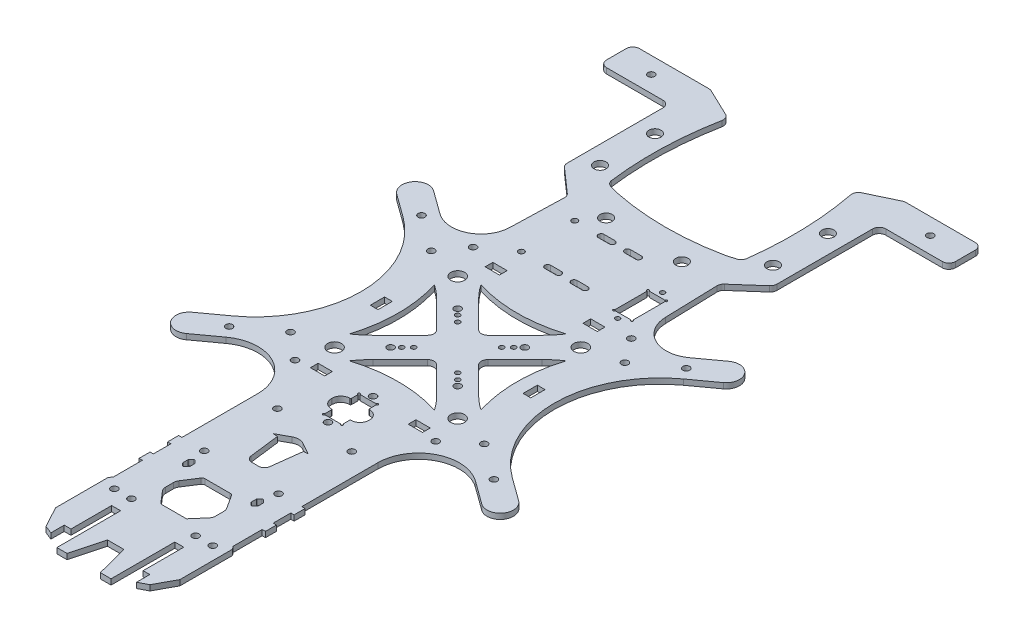
SolidWorks part; units mm, degrees
ref_plane "前视基准面" through (0, 0, 0) normal (0, 0, 1) x (1, 0, 0)
ref_plane "上视基准面" through (0, 0, 0) normal (0, 1, 0) x (1, 0, 0)
ref_plane "右视基准面" through (0, 0, 0) normal (1, 0, 0) x (0, 0, -1)
sketch "草图1" plane through (0, 0, 0) normal (0, 1, 0) x (1, 0, 0)
  line L0 (-126.4995, 0) -> (116.8967, 0) construction
  line L1 (121.619, 121.619) -> (-121.619, -121.619) construction
  line L2 (0, 104.5414) -> (0, -99.6328) construction
  line L3 (-108.3893, 108.3893) -> (124.9236, -124.9236) construction
  line L4 (0, 0) -> (86.3378, -62.728) construction
  line L5 (21.4, 65.75) -> (28.6, 65.75)
  line L6 (20.9, 50.75) -> (20.9, 65.25)
  line L19 (21.4, 50.25) -> (28.6, 50.25)
  line L20 (34.6494, 84.6384) -> (47.6818, 96.1449)
  line L21 (0, 82.79) -> (0, 88.225) construction
  line L22 (17.0991, -107.7737) -> (17.0991, -105.6162)
  line L23 (-24.5433, 97.1224) -> (-30.4982, 98.8019)
  line L24 (44.1232, 159.0629) -> (28.8407, 151.7785)
  line L25 (27.2573, -98.177) -> (28.7573, -98.177)
  line L26 (35.4016, 59.0549) -> (34.6494, 84.6384)
  line L27 (79.3904, 159.0629) -> (44.1232, 159.0629)
  line L28 (15.9026, -104.2126) -> (16.9526, -105.2626)
  line L29 (14.1455, -105.2626) -> (15.1955, -104.2126)
  line L30 (-16.9545, -108.1273) -> (-15.9045, -109.1773)
  line L31 (79.3904, 144.0629) -> (79.3904, 159.0629)
  line L32 (27.2573, -98.177) -> (27.2573, -63.5957)
  line L33 (67.2151, -56.251) -> (56.6859, -48.6011)
  line L34 (47.6818, 144.0629) -> (79.3904, 144.0629)
  line L35 (74.2685, -46.5428) -> (63.7393, -38.8929)
  line L36 (-15.1974, -109.1773) -> (-14.1474, -108.1273)
  line L37 (-14.0009, -105.6162) -> (-14.0009, -107.7737)
  line L38 (-14.1474, -105.2626) -> (-15.1974, -104.2126)
  line L39 (-47.6818, 96.1449) -> (-47.6818, 144.0629)
  line L40 (-34.6494, 84.6384) -> (-47.6818, 96.1449)
  line L41 (-35.4016, 59.0549) -> (-34.6494, 84.6384)
  line L42 (28.7573, -98.177) -> (28.7573, -103.177)
  line L59 (0, 72.0242) -> (0, 60.8242) construction
  line L64 (20.9, 58) -> (32.4846, 58) construction
  line L65 (25, 65.75) -> (25, 50.25) construction
  line L66 (29.1, 65.25) -> (29.1, 50.75)
  line L69 (-28.3, 64.3716) -> (-2.5276, 64.3716) construction
  line L72 (28.7573, -103.177) -> (27.2573, -103.177)
  line L80 (-15.9045, -104.2126) -> (-16.9545, -105.2626)
  line L81 (-17.1009, -107.7737) -> (-17.1009, -105.6162)
  line L82 (4.1009, -56.25) -> (4.1009, -53.2975)
  line L83 (-3.6009, -56.75) -> (3.6009, -56.75)
  line L84 (3.6009, -40.75) -> (-3.5991, -40.75)
  line L85 (4.1009, -41.25) -> (4.1009, -44.2025)
  line L86 (-4.1009, -56.25) -> (-4.1009, -53.2961)
  line L87 (-4.1009, -44.2011) -> (-4.1009, -41.2481)
  line L88 (-4.5484, -52.9461) -> (-4.4509, -52.9461)
  line L89 (-8.5484, -48.9461) -> (-8.5484, -48.5511)
  line L90 (8.5484, -48.9475) -> (8.5484, -48.5525)
  line L91 (4.4509, -52.9475) -> (4.5484, -52.9475)
  line L92 (4.5484, -44.5525) -> (4.4509, -44.5525)
  line L93 (-4.5484, -44.5511) -> (-4.4509, -44.5511)
  line L94 (13.9991, -105.6162) -> (13.9991, -107.7737)
  line L95 (15.1955, -109.1773) -> (14.1455, -108.1273)
  line L96 (16.9526, -108.1273) -> (15.9026, -109.1773)
  line L97 (18.9991, -62.5) -> (18.9991, -100.5) construction
  line L98 (18.9991, -100.5) -> (-19.0009, -100.5) construction
  line L99 (-19.0009, -62.5) -> (-19.0009, -100.5) construction
  line L100 (27.2573, -103.177) -> (27.2573, -111.177)
  line L101 (16.4174, -141.0041) -> (16.4174, -159.5041)
  line L102 (16.4174, -141.0041) -> (12.3174, -141.0041)
  line L103 (12.3174, -141.0041) -> (12.3174, -170.0041)
  line L104 (19.4666, -159.5041) -> (16.4174, -159.5041)
  line L105 (19.4666, -165.5542) -> (19.4666, -159.5041)
  line L106 (-3.8169, -155.5041) -> (-7.6919, -170.0041)
  line L107 (-7.6919, -170.0041) -> (-12.3174, -170.0041)
  line L108 (23.4926, -163.4505) -> (19.4666, -165.5542)
  line L109 (-19.4666, -165.5542) -> (-19.4666, -159.5041)
  line L110 (-19.4666, -159.5041) -> (-16.4174, -159.5041)
  line L111 (-12.3174, -141.0041) -> (-12.3174, -170.0041)
  line L112 (-16.4174, -141.0041) -> (-12.3174, -141.0041)
  line L113 (-16.4174, -141.0041) -> (-16.4174, -159.5041)
  line L114 (7.4592, -170.0041) -> (12.3174, -170.0041)
  line L115 (-3.8169, -155.5041) -> (3.6009, -155.5041)
  line L116 (3.6009, -155.5041) -> (7.4592, -170.0041)
  line L117 (-23.1028, -164.168) -> (-19.4666, -165.5542)
  line L118 (-10.8641, -115.9341) -> (-6.9283, -109.8213)
  line L119 (-10.5808, -123.7337) -> (-5.8541, -129.2069)
  line L120 (-5.8541, -129.2069) -> (5.8541, -129.2069)
  line L121 (-11.4015, -121.5278) -> (-11.4015, -117.7612)
  line L122 (27.2573, -111.177) -> (28.7573, -111.177)
  line L123 (28.2798, -130.7335) -> (28.2798, -154.6401)
  line L124 (28.2798, -154.6401) -> (23.4926, -163.4505)
  line L125 (-28.2798, -154.6401) -> (-23.1028, -164.168)
  line L126 (-28.2798, -130.7335) -> (-28.2798, -154.6401)
  line L127 (28.7573, -111.177) -> (28.7573, -116.177)
  line L128 (28.7573, -116.177) -> (27.2573, -116.177)
  line L129 (27.2573, -116.177) -> (27.2573, -129.3732)
  line L130 (27.2573, -129.3732) -> (28.2798, -130.7335)
  line L131 (-27.2573, -98.177) -> (-27.2573, -63.5957)
  line L132 (-27.2573, -129.3732) -> (-28.2798, -130.7335)
  line L133 (-27.2573, -116.177) -> (-27.2573, -129.3732)
  line L134 (-28.7573, -116.177) -> (-27.2573, -116.177)
  line L135 (-28.7573, -111.177) -> (-28.7573, -116.177)
  line L136 (-27.2573, -111.177) -> (-28.7573, -111.177)
  line L137 (-27.2573, -103.177) -> (-27.2573, -111.177)
  line L138 (-28.7573, -103.177) -> (-27.2573, -103.177)
  line L139 (-28.7573, -98.177) -> (-28.7573, -103.177)
  line L140 (-27.2573, -98.177) -> (-28.7573, -98.177)
  line L141 (-67.2151, 56.251) -> (-56.6859, 48.6011)
  line L142 (-74.2685, 46.5428) -> (-63.7393, 38.8929)
  line L143 (-74.2685, -46.5428) -> (-63.7393, -38.8929)
  line L144 (-67.2151, -56.251) -> (-56.6859, -48.6011)
  line L145 (-47.6818, 144.0629) -> (-79.3904, 144.0629)
  line L146 (-79.3904, 144.0629) -> (-79.3904, 159.0629)
  line L147 (-79.3904, 159.0629) -> (-44.1232, 159.0629)
  line L148 (-44.1232, 159.0629) -> (-28.8407, 151.7785)
  line L149 (47.6818, 96.1449) -> (47.6818, 144.0629)
  line L150 (0, -114.8485) -> (0, -146.3095) construction
  line L151 (-5.6802, -109.2069) -> (5.6802, -109.2069)
  line L152 (10.5808, -123.7337) -> (5.8541, -129.2069)
  line L153 (11.4015, -121.5278) -> (11.4015, -117.7612)
  line L154 (10.8641, -115.9341) -> (6.9283, -109.8213)
  line L155 (-19.0009, -62.5) -> (18.9991, -62.5) construction
  line L166 (-11.2799, 76.5216) -> (-6.2799, 76.5216) construction
  line L169 (-11.2799, 77.8216) -> (-6.2799, 77.8216)
  line L170 (-11.2799, 75.2216) -> (-6.2799, 75.2216)
  line L171 (-11.2799, 52.2216) -> (-6.2799, 52.2216) construction
  line L172 (-11.2799, 50.9216) -> (-6.2799, 50.9216)
  line L173 (-11.2799, 53.5216) -> (-6.2799, 53.5216)
  line L174 (5.7201, 76.5216) -> (0.7201, 76.5216) construction
  line L175 (5.7201, 75.2216) -> (0.7201, 75.2216)
  line L176 (5.7201, 77.8216) -> (0.7201, 77.8216)
  line L177 (5.7201, 52.2216) -> (0.7201, 52.2216) construction
  line L178 (5.7201, 53.5216) -> (0.7201, 53.5216)
  line L179 (5.7201, 50.9216) -> (0.7201, 50.9216)
  line L180 (74.2685, 46.5428) -> (63.7393, 38.8929)
  line L181 (44.0442, 32) -> (60.2246, 43.7557) construction
  line L182 (67.2151, 56.251) -> (56.6859, 48.6011)
  line L183 (24.5433, 97.1224) -> (30.4982, 98.8019)
  circle A0 centre (10, 10) radius 1.075
  circle A1 centre (12.75, 12.75) radius 1.075
  circle A2 centre (15.25, 15.25) radius 1.55
  circle A3 centre (-15.25, 15.25) radius 1.55
  circle A4 centre (-12.75, 12.75) radius 1.075
  circle A5 centre (-10, 10) radius 1.075
  circle A6 centre (-10, -10) radius 1.075
  circle A7 centre (-12.75, -12.75) radius 1.075
  circle A8 centre (-15.25, -15.25) radius 1.55
  circle A9 centre (15.25, -15.25) radius 1.55
  circle A10 centre (12.75, -12.75) radius 1.075
  circle A11 centre (10, -10) radius 1.075
  circle A14 centre (28, -28) radius 3.15
  circle A15 centre (-28, -28) radius 3.15
  circle A16 centre (25, 68.2) radius 1.05
  arc A17 (20.9, 65.25) -> (21.4, 65.75) centre (20.9, 65.75) cw
  arc A18 (20.9, 50.75) -> (21.4, 50.25) centre (20.9, 50.25) ccw
  circle A31 centre (25, 47.8) radius 1.05
  circle A34 centre (17.238, 84.7633) radius 2.75
  circle A35 centre (-17.238, 84.7633) radius 2.75
  circle A36 centre (-39.335, 104.0823) radius 2.75
  circle A37 centre (-39.335, 129.0823) radius 2.75
  circle A38 centre (-28, 28) radius 3.15
  circle A39 centre (28, 28) radius 3.15
  circle A42 centre (63.4501, 151.5629) radius 1.55
  circle A43 centre (44.0442, -32) radius 1.55
  circle A44 centre (60.2246, -43.7557) radius 1.55
  circle A47 centre (-60.2246, -43.7557) radius 1.55
  arc A63 (29.1, 65.25) -> (28.6, 65.75) centre (29.1, 65.75) ccw
  arc A64 (29.1, 50.75) -> (28.6, 50.25) centre (29.1, 50.25) cw
  circle A65 centre (-23.2799, 76.5216) radius 1.3
  circle A68 centre (-23.2799, 52.2216) radius 1.3
  circle A71 centre (-44.0442, -32) radius 1.55
  circle A72 centre (60.2246, 43.7557) radius 1.55
  circle A73 centre (44.0442, 32) radius 1.55
  circle A74 centre (-44.0442, 32) radius 1.55
  circle A75 centre (-60.2246, 43.7557) radius 1.55
  arc A76 (-11.2799, 77.8216) -> (-11.2799, 75.2216) centre (-11.2799, 76.5216) ccw
  arc A77 (67.2151, -56.251) -> (74.2685, -46.5428) centre (70.7418, -51.3969) ccw
  arc A78 (27.2573, -63.5957) -> (56.6859, -48.6011) centre (45.7917, -63.5957) cw
  arc A79 (-17.1009, -107.7737) -> (-16.9545, -108.1273) centre (-16.6009, -107.7737) ccw
  arc A80 (-15.9045, -109.1773) -> (-15.1974, -109.1773) centre (-15.5509, -108.8237) ccw
  arc A81 (-14.0009, -107.7737) -> (-14.1474, -108.1273) centre (-14.5009, -107.7737) cw
  arc A82 (-14.0009, -105.6162) -> (-14.1474, -105.2626) centre (-14.5009, -105.6162) ccw
  arc A83 (-15.1974, -104.2126) -> (-15.9045, -104.2126) centre (-15.5509, -104.5662) ccw
  arc A84 (-17.1009, -105.6162) -> (-16.9545, -105.2626) centre (-16.6009, -105.6162) cw
  arc A85 (-4.1009, -56.25) -> (-3.6009, -56.75) centre (-4.1009, -56.75) ccw
  arc A86 (4.1009, -56.25) -> (3.6009, -56.75) centre (4.1009, -56.75) cw
  arc A87 (4.1009, -41.25) -> (3.6009, -40.75) centre (4.1009, -40.75) ccw
  arc A88 (-4.1009, -41.2481) -> (-3.5991, -40.75) centre (-4.0991, -40.7481) cw
  arc A89 (8.5484, -48.5525) -> (4.5484, -44.5525) centre (4.5484, -48.5525) ccw
  arc A90 (-4.5484, -44.5511) -> (-8.5484, -48.5511) centre (-4.5484, -48.5511) ccw
  arc A91 (-4.5484, -52.9461) -> (-8.5484, -48.9461) centre (-4.5484, -48.9461) cw
  arc A92 (8.5484, -48.9475) -> (4.5484, -52.9475) centre (4.5484, -48.9475) cw
  arc A93 (4.1009, -44.2025) -> (4.4509, -44.5525) centre (4.4509, -44.2025) ccw
  arc A94 (4.1009, -53.2975) -> (4.4509, -52.9475) centre (4.4509, -53.2975) cw
  arc A95 (-4.1009, -44.2011) -> (-4.4509, -44.5511) centre (-4.4509, -44.2011) cw
  arc A96 (-4.1009, -53.2961) -> (-4.4509, -52.9461) centre (-4.4509, -53.2961) ccw
  arc A97 (17.0991, -107.7737) -> (16.9526, -108.1273) centre (16.5991, -107.7737) cw
  arc A98 (17.0991, -105.6162) -> (16.9526, -105.2626) centre (16.5991, -105.6162) ccw
  arc A99 (15.1955, -104.2126) -> (15.9026, -104.2126) centre (15.5491, -104.5662) cw
  arc A100 (13.9991, -105.6162) -> (14.1455, -105.2626) centre (14.4991, -105.6162) cw
  arc A101 (13.9991, -107.7737) -> (14.1455, -108.1273) centre (14.4991, -107.7737) ccw
  arc A102 (15.9026, -109.1773) -> (15.1955, -109.1773) centre (15.5491, -108.8237) cw
  circle A103 centre (-22.3899, -133.8062) radius 1.55
  circle A104 centre (22.3899, -133.8062) radius 1.55
  circle A105 centre (-16.9009, -98.4) radius 1.55
  circle A106 centre (16.8991, -98.4) radius 1.55
  arc A107 (-5.6802, -109.2069) -> (-6.9283, -109.8213) centre (-5.7932, -110.5521) ccw
  arc A108 (-11.4015, -117.7612) -> (-10.8641, -115.9341) centre (-8.0265, -117.7612) cw
  arc A109 (-10.5808, -123.7337) -> (-11.4015, -121.5278) centre (-8.0265, -121.5278) cw
  circle A110 centre (-14.6009, -133.8062) radius 1.55
  circle A111 centre (14.6009, -133.8062) radius 1.55
  arc A112 (10.5808, -123.7337) -> (11.4015, -121.5278) centre (8.0265, -121.5278) ccw
  arc A113 (11.4015, -117.7612) -> (10.8641, -115.9341) centre (8.0265, -117.7612) ccw
  arc A114 (5.6802, -109.2069) -> (6.9283, -109.8213) centre (5.7932, -110.5521) cw
  arc A132 (-6.2799, 75.2216) -> (-6.2799, 77.8216) centre (-6.2799, 76.5216) ccw
  arc A133 (-11.2799, 50.9216) -> (-11.2799, 53.5216) centre (-11.2799, 52.2216) cw
  arc A134 (-6.2799, 53.5216) -> (-6.2799, 50.9216) centre (-6.2799, 52.2216) cw
  arc A135 (5.7201, 75.2216) -> (5.7201, 77.8216) centre (5.7201, 76.5216) ccw
  arc A136 (0.7201, 77.8216) -> (0.7201, 75.2216) centre (0.7201, 76.5216) ccw
  arc A137 (5.7201, 53.5216) -> (5.7201, 50.9216) centre (5.7201, 52.2216) cw
  arc A138 (0.7201, 50.9216) -> (0.7201, 53.5216) centre (0.7201, 52.2216) cw
  arc A141 (-28.8407, 151.7785) -> (-30.4982, 98.8019) centre (122.812, 120.5195) ccw
  arc A142 (28.8407, 151.7785) -> (30.4982, 98.8019) centre (-122.812, 120.5195) cw
  circle A143 centre (-16.9009, -65.108) radius 1.55
  circle A144 centre (16.9009, -65.108) radius 1.55
  circle A145 centre (0, -38.5) radius 1.55
  circle A146 centre (0, -59) radius 1.55
  arc A147 (67.2151, 56.251) -> (74.2685, 46.5428) centre (70.7418, 51.3969) cw
  arc A148 (63.7393, 38.8929) -> (63.7393, -38.8929) centre (91.9966, 0) ccw
  circle A149 centre (44.0442, -32) radius 6 construction
  arc A150 (35.4016, 59.0549) -> (56.6859, 48.6011) centre (48.8045, 59.4489) ccw
  arc A151 (-67.2151, 56.251) -> (-74.2685, 46.5428) centre (-70.7418, 51.3969) ccw
  arc A152 (-35.4016, 59.0549) -> (-56.6859, 48.6011) centre (-48.8045, 59.4489) cw
  arc A153 (-63.7393, 38.8929) -> (-63.7393, -38.8929) centre (-91.9966, 0) cw
  arc A154 (-67.2151, -56.251) -> (-74.2685, -46.5428) centre (-70.7418, -51.3969) cw
  arc A155 (-27.2573, -63.5957) -> (-56.6859, -48.6011) centre (-45.7917, -63.5957) ccw
  circle A156 centre (-63.4501, 151.5629) radius 1.55
  circle A158 centre (39.335, 129.0823) radius 2.75
  circle A159 centre (39.335, 104.0823) radius 2.75
  arc A160 (-24.5433, 97.1224) -> (24.5433, 97.1224) centre (0, 215.2587) ccw
  circle A161 centre (-36, 43) radius 1.55
  circle A164 centre (36, 43) radius 1.55
  circle A165 centre (-32, -42) radius 1.55
  circle A166 centre (32, -42) radius 1.55
  point P47 (-8.7799, 76.5216)
  point P62 (-30.4982, 98.8019)
  point P66 (-24.5433, 97.1224)
  point P110 (3.2201, 76.5216)
  point P115 (-8.7799, 52.2216)
  point P171 (3.2201, 52.2216)
  point P354 (0, -129.2069)
  point P361 (7.3036, -118.1341)
  point P364 (0, -109.2069)
  dimension "D2" = 2.15
  dimension "D5" = 3.1
  dimension "D7" = 3.1
  dimension "D8" = 36
  dimension "D10" = 0.5
  dimension "D11" = 3.1
  dimension "D20" = 2.6
  dimension "D22" = 3.1
  dimension "D32" = 5
  dimension "D12" = 12
  dimension "D15" = 12
  dimension "D13" = 5
  dimension "D9" = 3.1
  dimension "D25" = 12
  dimension "D26" = 13
  dimension "D31" = 12
  dimension "D41" = 3.1
  dimension "D49" = 32
  dimension "D3" = 10
  dimension "D4" = 2.75
  dimension "D6" = 2.5
  dimension "D14" = 58
  dimension "D16" = 2.608
  dimension "D17" = 15.5
  dimension "D18" = 2.45
  dimension "D19" = 8.2
  dimension "D21" = 24.3
  dimension "D23" = 2.25
  dimension "D24" = 2.25
  dimension "D27" = 20
  dimension "D28" = 25
  dimension "D29" = 25
  dimension "D30" = 32
  dimension "D33" = 1.5
  dimension "D34" = 2.1
  dimension "D35" = 10.5
  dimension "D36" = 14.5
  dimension "D37" = 4
  dimension "D38" = 4.1
  dimension "D39" = 8
  dimension "D40" = 15
  dimension "D42" = 7.5
  dimension "D43" = 43
  dimension "D44" = 20
  dimension "D45" = 40.75
  dimension "D46" = 7.2
  dimension "D47" = 16
  dimension "D48" = 62.5
  dimension "D50" = 38
  dimension "D51" = 7.2
  dimension "D52" = 36
  dimension "D53" = 42
extrude "凸台-拉伸1" add sketch "草图1" along normal blind 2.5
sketch "草图6" plane through (0, 2.5, 0) normal (0, 1, 0) x (1, 0, 0)
  line L1 (-23.978, 14.4296) -> (-9.5485, 0)
  line L2 (-126.4995, 0) -> (116.8967, 0) construction
  line L3 (-58.8867, 0) -> (57.6096, 0) construction
  line L4 (-23.978, -14.4296) -> (-9.5485, 0)
  line L5 (0, 29.8455) -> (0, -115.5328) construction
  line L6 (0, 104.5414) -> (0, -99.6328) construction
  line L14 (14.4296, 23.978) -> (0, 9.5485)
  line L15 (-14.4296, 23.978) -> (0, 9.5485)
  line L20 (2.5276, -72.9435) -> (7.8986, -75.8938)
  line L21 (-7.8986, -75.8938) -> (-2.5276, -72.9435)
  line L22 (-1.6288, -92.0995) -> (1.6288, -92.0995)
  line L23 (-5.924, -76.1216) -> (-4.2339, -89.7964)
  line L24 (5.924, -76.1216) -> (4.2339, -89.7964)
  line L25 (-7.8986, -75.8938) -> (-5.924, -76.1216)
  line L26 (7.8986, -75.8938) -> (5.924, -76.1216)
  line L27 (23.978, -14.4296) -> (9.5485, 0)
  line L28 (23.978, 14.4296) -> (9.5485, 0)
  line L29 (-14.4296, -23.978) -> (0, -9.5485)
  line L30 (14.4296, -23.978) -> (0, -9.5485)
  arc A3 (-23.978, 14.4296) -> (-29.9602, 19.3706) centre (-52.8883, -14.4807) ccw
  arc A5 (-23.978, -14.4296) -> (-29.9602, -19.3706) centre (-52.8883, 14.4807) cw
  arc A6 (-29.9602, -19.3706) -> (-29.9602, 19.3706) centre (-91.9966, 0) ccw
  arc A18 (-14.4296, 23.978) -> (-19.3706, 29.9602) centre (14.4807, 52.8883) cw
  arc A19 (-19.3706, 29.9602) -> (19.3706, 29.9602) centre (0, 91.9966) ccw
  arc A20 (14.4296, 23.978) -> (19.3706, 29.9602) centre (-14.4807, 52.8883) ccw
  arc A27 (2.5276, -72.9435) -> (-2.5276, -72.9435) centre (0, -77.545) ccw
  arc A28 (1.6288, -92.0995) -> (4.2339, -89.7964) centre (1.6288, -89.4745) ccw
  arc A29 (-1.6288, -92.0995) -> (-4.2339, -89.7964) centre (-1.6288, -89.4745) cw
  arc A30 (23.978, 14.4296) -> (29.9602, 19.3706) centre (52.8883, -14.4807) cw
  arc A31 (29.9602, 19.3706) -> (29.9602, -19.3706) centre (91.9966, 0) ccw
  arc A32 (23.978, -14.4296) -> (29.9602, -19.3706) centre (52.8883, 14.4807) ccw
  arc A33 (14.4296, -23.978) -> (19.3706, -29.9602) centre (-14.4807, -52.8883) cw
  arc A34 (19.3706, -29.9602) -> (-19.3706, -29.9602) centre (0, -91.9966) ccw
  arc A35 (-14.4296, -23.978) -> (-19.3706, -29.9602) centre (14.4807, -52.8883) ccw
  dimension "D1" = 45
  dimension "D2" = 4
extrude "减重" cut sketch "草图6" against normal up to next
fillet "圆角1" radius 3 22 edges at (79.3904, 1.25, -159.0629) (79.3904, 1.25, -144.0629) (47.6818, 1.25, -144.0629) (44.1232, 1.25, -159.0629) (28.8407, 1.25, -151.7785) (-79.3904, 1.25, -159.0629) (-79.3904, 1.25, -144.0629) (-47.6818, 1.25, -144.0629) (-44.1232, 1.25, -159.0629) (-28.8407, 1.25, -151.7785) (-24.5433, 1.25, -97.1224) (-30.4982, 1.25, -98.8019) (24.5433, 1.25, -97.1224) (30.4982, 1.25, -98.8019) (-34.6494, 1.25, -84.6384) (34.6494, 1.25, -84.6384) (47.6818, 1.25, -96.1449) (-47.6818, 1.25, -96.1449) (-9.5485, 1.25, 0) (9.5485, 1.25, 0) (0, 1.25, -9.5485) (0, 1.25, 9.5485)
sketch "草图7" plane through (0, 2.5, 0) normal (0, 1, 0) x (1, 0, 0)
  line L0 (-81.2345, 0) -> (102.1666, 0) construction
  line L1 (0, 63.5408) -> (0, -83.9036) construction
  line L2 (36.5, -3.25) -> (33, -3.25)
  line L3 (-36.5, 3.25) -> (-33, 3.25)
  line L4 (-36.5, 3.25) -> (-36.5, -3.25)
  line L5 (-36.5, -3.25) -> (-33, -3.25)
  line L6 (-33, 3.25) -> (-33, -3.25)
  line L7 (33, 3.25) -> (33, -3.25)
  line L8 (36.5, 3.25) -> (33, 3.25)
  line L9 (36.5, 3.25) -> (36.5, -3.25)
  line L10 (19, -38) -> (25.5, -38)
  line L11 (-25.5, 41.5) -> (-19, 41.5)
  line L12 (-25.5, 41.5) -> (-25.5, 38)
  line L13 (-25.5, 38) -> (-19, 38)
  line L14 (-19, 41.5) -> (-19, 38)
  line L15 (19, -38) -> (19, -41.5)
  line L16 (19, -41.5) -> (25.5, -41.5)
  line L17 (25.5, -38) -> (25.5, -41.5)
  line L18 (-19, -38) -> (-19, -41.5)
  line L19 (-19, -41.5) -> (-25.5, -41.5)
  line L20 (-25.5, -38) -> (-25.5, -41.5)
  line L21 (-19, -38) -> (-25.5, -38)
  line L22 (25.5, 38) -> (19, 38)
  line L23 (19, 41.5) -> (19, 38)
  line L24 (25.5, 41.5) -> (19, 41.5)
  line L25 (25.5, 41.5) -> (25.5, 38)
  point P26 (19, -39.75)
  dimension "D1" = 3.5
  dimension "D2" = 6.5
  dimension "D3" = 33
  dimension "D4" = 38
  dimension "D5" = 19
  dimension "D6" = 38
extrude "保护壳固定点" cut sketch "草图7" against normal up to next
